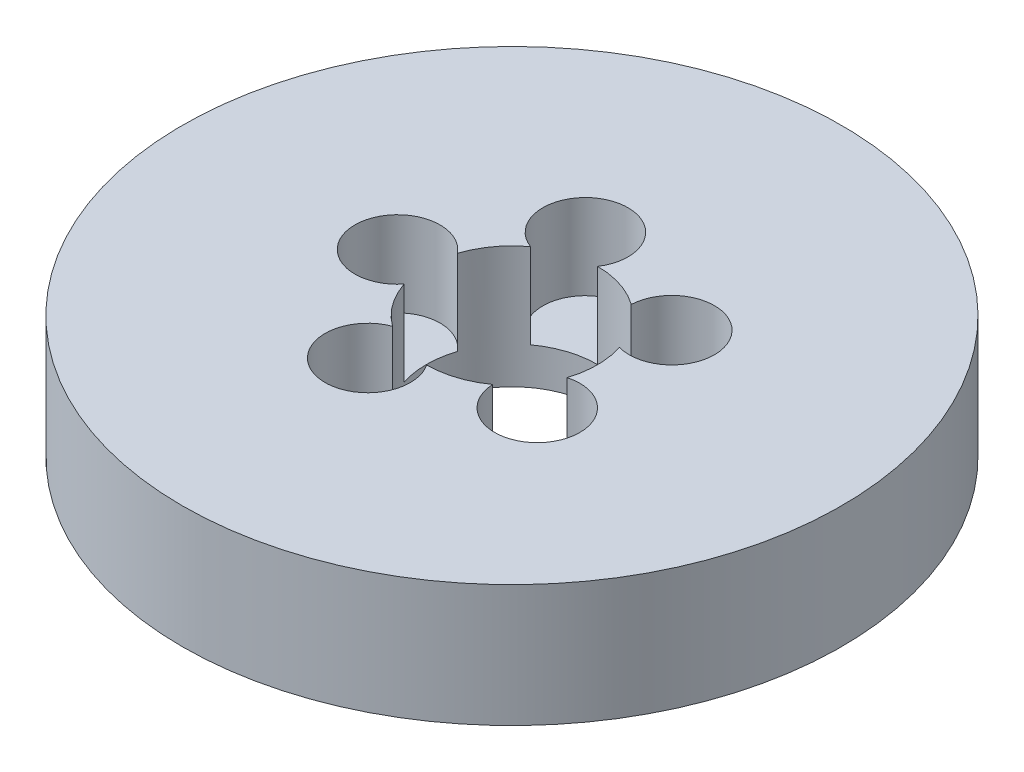
SolidWorks part; units mm, degrees
ref_plane "Front Plane" through (0, 0, 0) normal (0, 0, 1) x (1, 0, 0)
ref_plane "Top Plane" through (0, 0, 0) normal (0, 1, 0) x (1, 0, 0)
ref_plane "Right Plane" through (0, 0, 0) normal (1, 0, 0) x (0, 0, -1)
sketch "Sketch1" plane through (0, 0, 0) normal (0, 1, 0) x (1, 0, 0)
  circle A0 centre (0, 0) radius 67.5
  dimension "FLANGE_OD" = 135
extrude "Boss-Extrude1" add sketch "Sketch1" along normal blind 25
sketch "Sketch2" plane through (0, 0, 0) normal (0, 1, 0) x (1, 0, 0)
  circle A0 centre (0, 0) radius 17.5
  dimension "BORE_D" = 35
extrude "Cut-Extrude1" cut sketch "Sketch2" along normal through all
sketch "Sketch3" plane through (0, 25, 0) normal (0, 1, 0) x (1, 0, 0)
  circle A0 centre (0, 0) radius 23.4415 construction
  circle A1 centre (-23.4415, 0) radius 8.7295
  dimension "BOLT_D" = 17.4589
  dimension "BOLT_PCD" = 46.883
extrude "Cut-Extrude2" cut sketch "Sketch3" against normal blind 17.4133
pattern_circular "CirPattern1" count 5 over 360 about axis through (0, 0, 0) along (0, 1, 0) of "Cut-Extrude2"
